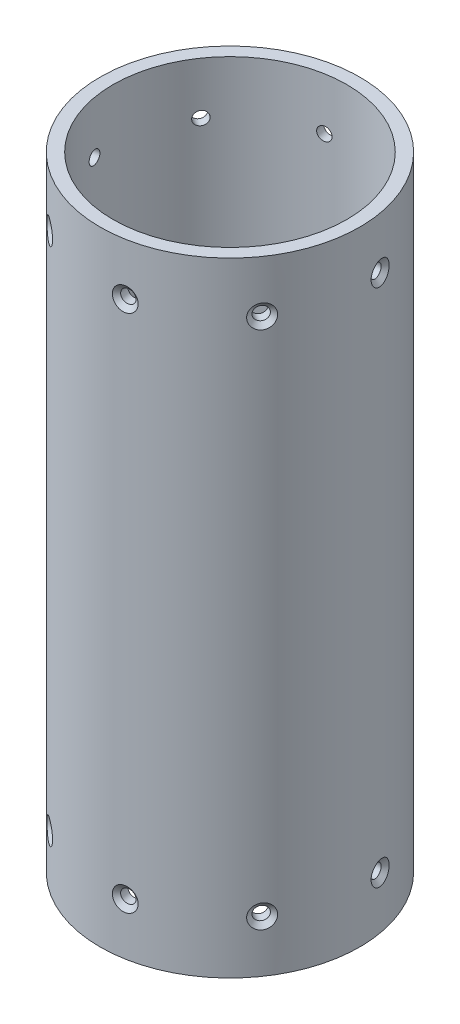
SolidWorks part; units mm, degrees
ref_plane "Front Plane" through (0, 0, 0) normal (0, 0, 1) x (1, 0, 0)
ref_plane "Top Plane" through (0, 0, 0) normal (0, 1, 0) x (1, 0, 0)
ref_plane "Right Plane" through (0, 0, 0) normal (1, 0, 0) x (0, 0, -1)
sketch "Sketch1" plane through (0, 0, 0) normal (0, 1, 0) x (1, 0, 0)
  circle A0 centre (-3.2883, -10.7506) radius 31.75
  circle A1 centre (-3.2883, -10.7506) radius 28.575
  dimension "D1" = 63.5
  dimension "D2" = 57.15
extrude "Boss-Extrude1" add sketch "Sketch1" along normal blind 152.4
hole_wizard "CSK for #4 Flat Head Machine Screw (100)1" positions "3DSketch2" profile "Sketch3" countersink size "#4" standard "ANSI Inch" end condition up to next
sketch3d "3DSketch2"
  point P0 (22.7602, 139.7, 28.9038)
  dimension "D1" = 12.7
sketch "Sketch3" plane through (22.7602, 139.7, 28.9038) normal (0, 1, 0) x (0.5718, 0, -0.8204)
  line L0 (0, 0) -> (0, 3.175)
  line L1 (0, 3.175) -> (1.6256, 3.175)
  line L2 (1.6256, 3.175) -> (1.6256, 1.0337)
  line L3 (1.6256, 1.0337) -> (2.8575, 0)
  line L5 (2.8575, 0) -> (0, 0)
  line L6 (-1.6256, 1.0337) -> (-2.8575, 0) construction
  line L11 (0, -6.35) -> (0, 107.95) construction
  dimension "Thru Hole Dia." = 3.2512
  dimension "Thru Hole Depth" = 3.175
  dimension "Near C'Sink Dia." = 5.715
  dimension "Near C'Sink Angle" = 100
pattern_circular "CirPattern1" count 8 over 360 about axis through (-3.2883, 152.4, 10.7506) along (0, -1, 0) of "CSK for #4 Flat Head Machine Screw (100)1"
pattern_linear "LPattern1" count 2 spacing 127 along (0, -1, 0) of "CirPattern1"
